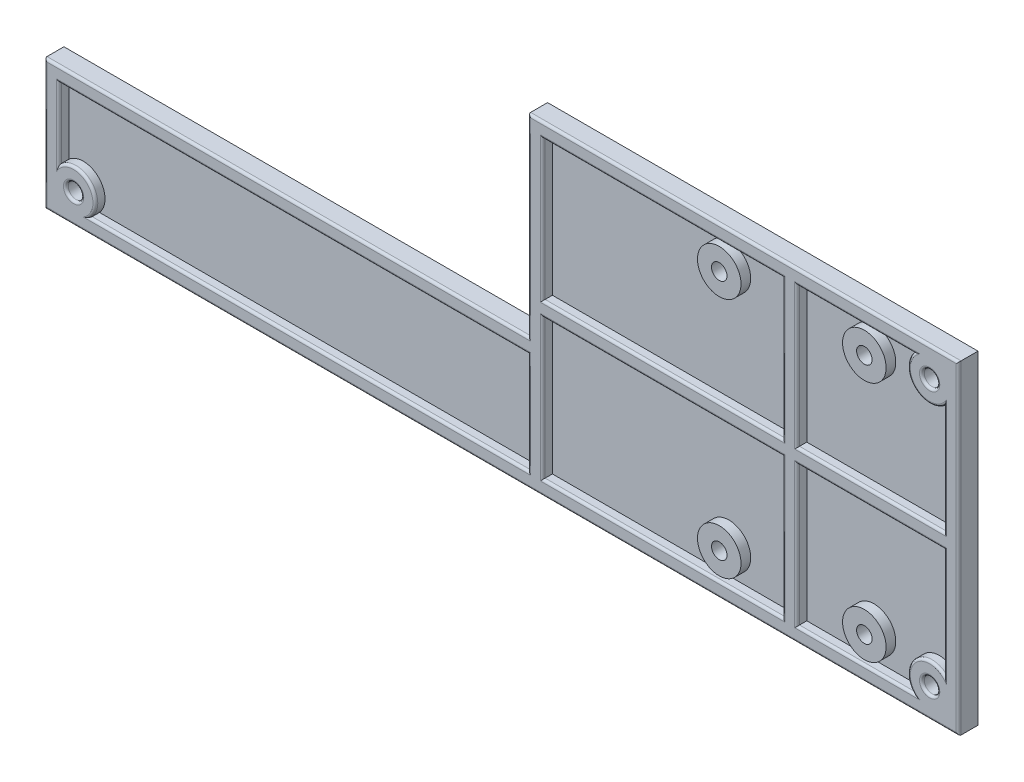
SolidWorks part; units mm, degrees
ref_plane "Plan de face" through (0, 0, 0) normal (0, 0, 1) x (1, 0, 0)
ref_plane "Plan de dessus" through (0, 0, 0) normal (0, 1, 0) x (1, 0, 0)
ref_plane "Plan de droite" through (0, 0, 0) normal (1, 0, 0) x (0, 0, -1)
sketch "Esquisse1" plane through (0, 0, 0) normal (0, 0, 1) x (1, 0, 0)
  line L0 (0, 0) -> (60, 0) construction
  line L1 (88.5, 27.5) -> (-88.5, 27.5) construction
  line L2 (88.5, 27.5) -> (88.5, -27.5) construction
  line L3 (88.5, -27.5) -> (-88.5, -27.5) construction
  line L4 (-88.5, 27.5) -> (-88.5, -27.5) construction
  line L5 (88.5, 27.5) -> (-88.5, -27.5) construction
  line L6 (88.5, -27.5) -> (-88.5, 27.5) construction
  line L7 (75, 25) -> (45, 25) construction
  line L8 (75, 25) -> (75, -25) construction
  line L9 (75, -25) -> (45, -25) construction
  line L10 (45, 25) -> (45, -25) construction
  line L11 (75, 25) -> (45, -25) construction
  line L12 (75, -25) -> (45, 25) construction
  line L14 (94.5, 33.5) -> (-94.5, 33.5)
  line L15 (94.5, 33.5) -> (94.5, -33.5)
  line L16 (94.5, -33.5) -> (-94.5, -33.5)
  line L17 (-94.5, 33.5) -> (-94.5, -33.5)
  line L18 (94.5, 33.5) -> (-94.5, -33.5) construction
  line L19 (94.5, -33.5) -> (-94.5, 33.5) construction
  circle A0 centre (-88.5, -27.5) radius 1.6
  circle A1 centre (88.5, 27.5) radius 1.6
  circle A2 centre (88.5, -27.5) radius 1.6
  circle A3 centre (-88.5, 27.5) radius 1.6
  circle A4 centre (45, 25) radius 1.6
  circle A5 centre (75, 25) radius 1.6
  circle A6 centre (45, -25) radius 1.6
  circle A7 centre (75, -25) radius 1.6
  point P0 (0, 0)
  point P10 (60, 0)
  dimension "D1" = 3.2
  dimension "D2" = 3.2
  dimension "D3" = 3.2
  dimension "D4" = 3.2
  dimension "D10" = 3.2
  dimension "D11" = 3.2
  dimension "D12" = 3.2
  dimension "D13" = 3.2
  dimension "D5" = 177
  dimension "D6" = 55
  dimension "D7" = 30
  dimension "D8" = 50
  dimension "D9" = 60
  dimension "D14" = 6
  dimension "D15" = 6
extrude "Boss.-Extru.1" add sketch "Esquisse1" along normal blind 2
sketch "Esquisse2" plane through (0, 0, 2) normal (0, 0, 1) x (1, 0, 0)
  line L1 (-94.5, 33.5) -> (5.5, 33.5)
  line L2 (-94.5, 33.5) -> (-94.5, -6.5)
  line L3 (-94.5, -6.5) -> (5.5, -6.5)
  line L4 (5.5, 33.5) -> (5.5, -6.5)
  dimension "D1" = 40
  dimension "D2" = 100
extrude "Enlèv. mat.-Extru.1" cut sketch "Esquisse2" against normal blind 2
sketch "Esquisse3" plane through (0, 0, 2) normal (0, 0, 1) x (1, 0, 0)
  line L6 (94.5, 33.5) -> (5.5, 33.5)
  line L7 (5.5, 33.5) -> (5.5, -6.5)
  line L8 (5.5, -6.5) -> (-94.5, -6.5)
  line L9 (-94.5, -6.5) -> (-94.5, -33.5)
  line L10 (-94.5, -33.5) -> (94.5, -33.5)
  line L11 (94.5, -33.5) -> (94.5, 33.5)
  line L12 (94.5, 33.5) -> (5.5, 33.5)
  line L13 (5.5, 33.5) -> (5.5, -6.5)
  line L14 (5.5, -6.5) -> (-94.5, -6.5)
  line L15 (-94.5, -6.5) -> (-94.5, -33.5)
  line L16 (-94.5, -33.5) -> (94.5, -33.5)
  line L17 (94.5, -33.5) -> (94.5, 33.5)
  line L24 (91.5, 30.5) -> (8.5, 30.5)
  line L25 (8.5, 30.5) -> (8.5, -9.5)
  line L26 (8.5, -9.5) -> (-91.5, -9.5)
  line L27 (-91.5, -9.5) -> (-91.5, -30.5)
  line L28 (-91.5, -30.5) -> (91.5, -30.5)
  line L29 (91.5, -30.5) -> (91.5, 30.5)
  line L30 (91.5, 30.5) -> (8.5, 30.5)
  line L31 (8.5, 30.5) -> (8.5, -9.5)
  line L32 (8.5, -9.5) -> (-91.5, -9.5)
  line L33 (-91.5, -9.5) -> (-91.5, -30.5)
  line L34 (-91.5, -30.5) -> (91.5, -30.5)
  line L35 (91.5, -30.5) -> (91.5, 30.5)
  dimension "D1" = 0
  dimension "D2" = 3
extrude "Boss.-Extru.2" add sketch "Esquisse3" along normal blind 2
sketch "Esquisse4" plane through (0, 0, 2) normal (0, 0, 1) x (1, 0, 0)
  line L0 (-94.5, -33.5) -> (94.5, -33.5) construction
  line L1 (5.5, -6.5) -> (8.5, -6.5)
  line L2 (5.5, -6.5) -> (5.5, -33.5)
  line L3 (5.5, -33.5) -> (8.5, -33.5)
  line L4 (8.5, -6.5) -> (8.5, -33.5)
  line L5 (8.5, 30.5) -> (8.5, -9.5) construction
  line L6 (5.5, 33.5) -> (5.5, -6.5) construction
  line L7 (5.5, 1.5) -> (94.5, 1.5)
  line L8 (5.5, 1.5) -> (5.5, -1.5)
  line L9 (5.5, -1.5) -> (94.5, -1.5)
  line L10 (94.5, 1.5) -> (94.5, -1.5)
  line L11 (94.5, -33.5) -> (94.5, 33.5) construction
  line L12 (0, 0) -> (94.5, 0) construction
  dimension "D1" = 3
extrude "Boss.-Extru.3" add sketch "Esquisse4" along normal blind 2
sketch "Esquisse5" plane through (0, 0, 2) normal (0, 0, 1) x (1, 0, 0)
  line L0 (59.5992, 30.5) -> (59.5992, -30.5) construction
  line L1 (91.5, 30.5) -> (8.5, 30.5) construction
  line L2 (8.5, -30.5) -> (91.5, -30.5) construction
  line L4 (61.0992, -30.5) -> (58.0992, -30.5)
  line L5 (61.0992, -30.5) -> (61.0992, 30.5)
  line L6 (61.0992, 30.5) -> (58.0992, 30.5)
  line L7 (58.0992, -30.5) -> (58.0992, 30.5)
  line L8 (61.0992, -30.5) -> (58.0992, 30.5) construction
  line L9 (61.0992, 30.5) -> (58.0992, -30.5) construction
  point P6 (59.5992, 0)
  dimension "D1" = 3
extrude "Boss.-Extru.4" add sketch "Esquisse5" along normal blind 2
sketch "Esquisse6" plane through (0, 0, 2) normal (0, 0, 1) x (1, 0, 0)
  circle A0 centre (-88.5, -27.5) radius 1.6 construction
  circle A1 centre (-88.5, -27.5) radius 1.6
  circle A2 centre (-88.5, -27.5) radius 4.5
  circle A3 centre (88.5, -27.5) radius 4.5
  circle A4 centre (75, -25) radius 4.5
  circle A5 centre (45, -25) radius 4.5
  circle A6 centre (45, 25) radius 4.5
  circle A7 centre (75, 25) radius 4.5
  circle A8 centre (88.5, 27.5) radius 4.5
  circle A9 centre (45, -25) radius 1.6 construction
  circle A10 centre (45, -25) radius 1.6
  circle A11 centre (45, 25) radius 1.6 construction
  circle A12 centre (45, 25) radius 1.6
  circle A13 centre (75, 25) radius 1.6 construction
  circle A14 centre (75, 25) radius 1.6
  circle A15 centre (88.5, 27.5) radius 1.6 construction
  circle A16 centre (88.5, 27.5) radius 1.6
  circle A17 centre (88.5, -27.5) radius 1.6 construction
  circle A18 centre (88.5, -27.5) radius 1.6
  circle A19 centre (75, -25) radius 1.6 construction
  circle A20 centre (75, -25) radius 1.6
  point P21 (45, -25)
  dimension "D1" = 9
  dimension "D2" = 9
  dimension "D3" = 9
  dimension "D4" = 9
  dimension "D5" = 9
  dimension "D6" = 9
  dimension "D7" = 9
extrude "Boss.-Extru.5" add sketch "Esquisse6" along normal blind 2
fillet "Congé1" radius 0.5 32 edges at (90.1, 27.5, 4) (90.1, -27.5, 4) (-86.9, -27.5, 4) (50, 33.5, 4) (94.5, 0, 4) (0, -33.5, 4) (-94.5, -20, 4) (-44.5, -6.5, 4) (5.5, 13.5, 4) (33.2996, -1.5, 4) (8.5, -16, 4) (33.2996, -30.5, 4) (58.0992, -16, 4) (76.2996, -1.5, 4) (61.0992, -16, 4) (73.1225, -30.5, 4) (85.318, -24.318, 4) (91.5, -12.8229, 4) (33.2996, 30.5, 4) (8.5, 16, 4) (33.2996, 1.5, 4) (58.0992, 16, 4) (5.5, -20, 4) (-43, -9.5, 4) (-91.5, -16.8229, 4) (-85.318, -24.318, 4) (-39.8229, -30.5, 4) (61.0992, 16, 4) (76.2996, 1.5, 4) (91.5, 12.8229, 4) (85.318, 24.318, 4) (73.1225, 30.5, 4)
